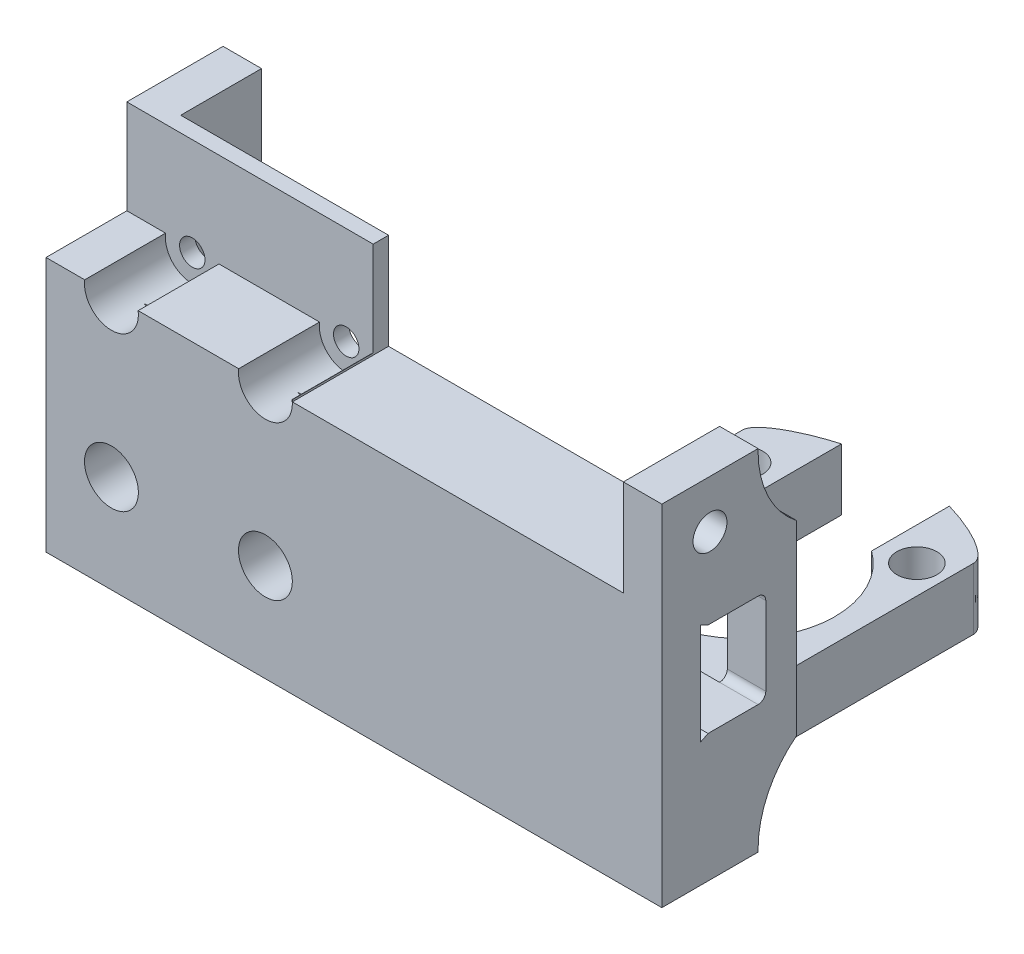
SolidWorks part; units mm, degrees
ref_plane "Front Plane" through (0, 0, 0) normal (0, 0, 1) x (1, 0, 0)
ref_plane "Top Plane" through (0, 0, 0) normal (0, 1, 0) x (1, 0, 0)
ref_plane "Right Plane" through (0, 0, 0) normal (1, 0, 0) x (0, 0, -1)
sketch "Sketch1" plane through (0, 0, 0) normal (0, 0, 1) x (1, 0, 0)
  line L1 (0, 0) -> (80, 0)
  line L2 (0, 0) -> (0, 45.4)
  line L3 (0, 45.4) -> (80, 45.4)
  line L4 (80, 0) -> (80, 45.4)
  line L5 (8.5, 32.7) -> (28.5, 32.7) construction
  line L6 (8.5, 32.7) -> (8.5, 12.7) construction
  line L7 (8.5, 12.7) -> (28.5, 12.7) construction
  line L8 (28.5, 32.7) -> (28.5, 12.7) construction
  circle A0 centre (8.5, 32.7) radius 1.65
  circle A1 centre (28.5, 32.7) radius 1.65
  circle A2 centre (28.5, 12.7) radius 1.65
  circle A3 centre (8.5, 12.7) radius 1.65
  dimension "D3" = 3.3
  dimension "D1" = 45.4
  dimension "D2" = 80
  dimension "D4" = 12.7
  dimension "D5" = 20
  dimension "D6" = 8.5
extrude "Boss-Extrude1" add sketch "Sketch1" along normal blind 12.5
sketch "Sketch2" plane through (0, 0, 0) normal (0, 0, -1) x (-1, 0, 0)
  line L0 (0, 0) -> (-80, 0) construction
  line L1 (0, 45.4) -> (-5, 45.4)
  line L2 (0, 45.4) -> (0, 0)
  line L3 (0, 0) -> (-5, 0)
  line L4 (-5, 45.4) -> (-5, 0)
  dimension "D1" = 5
extrude "Boss-Extrude2" add sketch "Sketch2" along normal blind 10.5
sketch "Sketch3" plane through (0, 0, 0) normal (0, 0, 1) x (1, 0, 0)
  line L0 (80, 0) -> (80, 45.4) construction
  line L1 (80, 28.8) -> (0, 28.8)
  line L2 (80, 28.8) -> (80, 16.6)
  line L3 (80, 16.6) -> (0, 16.6)
  line L4 (0, 28.8) -> (0, 16.6)
  line L5 (0, 0) -> (0, 45.4) construction
  line L6 (80, 22.7) -> (0, 22.7) construction
  point P10 (80, 22.7)
  dimension "D1" = 12.2
extrude "Cut-Extrude1" cut sketch "Sketch3" against normal through all and the other way blind 7.5
sketch "Sketch4" plane through (0, 0, 0) normal (0, 0, -1) x (-1, 0, 0)
  line L1 (-69.5, 0) -> (-39.5, 0)
  line L2 (-69.5, 0) -> (-69.5, 8)
  line L3 (-69.5, 8) -> (-39.5, 8)
  line L4 (-39.5, 0) -> (-39.5, 8)
  line L7 (-5, 0) -> (-80, 0) construction
  dimension "D1" = 8
  dimension "D2" = 30
  dimension "D3" = 39.5
extrude "Boss-Extrude3" add sketch "Sketch4" along normal blind 44.5
sketch "Sketch5" plane through (0, 8, 0) normal (0, 1, 0) x (1, 0, 0)
  line L0 (69.5, 44.5) -> (69.5, 0) construction
  line L1 (80, 0) -> (5, 0) construction
  circle A0 centre (54.4956, 23.5) radius 12
  dimension "D1" = 24
  dimension "D2" = 15.0044
  dimension "D3" = 23.5
extrude "Cut-Extrude2" cut sketch "Sketch5" against normal blind 45
sketch "Sketch6" plane through (0, 16.6, 0) normal (0, -1, 0) x (1, 0, 0)
  circle A3 centre (54.4956, -39.5013) radius 2.6
  circle A4 centre (65.8093, -34.815) radius 2.6
  circle A5 centre (43.1819, -34.815) radius 2.6
  dimension "D1" = 5.2
extrude "Cut-Extrude3" cut sketch "Sketch6" against normal through all both and the other way through all
fillet "Fillet1" radius 6 2 edges at (39.5, 4, -44.5) (69.5, 4, -44.5) second distance 15 conic rho 0.3 first distance on face at (39.5, 4, -22.25) first distance on face at (69.5, 4, -22.25)
sketch "Sketch8" plane through (0, 0, 12.5) normal (0, 0, 1) x (1, 0, 0)
  circle A0 centre (8.5, 32.7) radius 3.5
  circle A1 centre (28.5, 32.7) radius 3.5
  circle A2 centre (8.5, 12.7) radius 3.5
  circle A3 centre (28.5, 12.7) radius 3.5
  dimension "D1" = 7
extrude "Cut-Extrude5" cut sketch "Sketch8" against normal offset from surface (10.5 mm away) 2 up to face at (10.15, 12.7, 0)
sketch "Sketch12" plane through (0, 0, 12.5) normal (0, 0, 1) x (1, 0, 0)
  line L0 (80, 45.4) -> (0, 45.4) construction
  line L5 (0, 45.4) -> (45, 45.4)
  line L6 (0, 45.4) -> (0, 33.15)
  line L7 (0, 33.15) -> (45, 33.15)
  line L8 (45, 45.4) -> (45, 33.15)
  line L9 (0, 45.4) -> (0, 0) construction
  dimension "D1" = 12.25
  dimension "D2" = 45
extrude "Cut-Extrude8" cut sketch "Sketch12" against normal offset from surface (10.5 mm away) 2 up to face at (10.15, 32.7, 0)
sketch "Sketch13" plane through (0, 8, 0) normal (0, 1, 0) x (1, 0, 0)
  line L1 (61.4956, 51.1384) -> (47.4956, 51.1384)
  line L2 (61.4956, 51.1384) -> (61.4956, 27.8643)
  line L3 (61.4956, 27.8643) -> (47.4956, 27.8643)
  line L4 (47.4956, 51.1384) -> (47.4956, 27.8643)
  line L5 (61.4956, 51.1384) -> (47.4956, 27.8643) construction
  line L6 (61.4956, 27.8643) -> (47.4956, 51.1384) construction
  point P0 (54.4956, 39.5013)
  dimension "D1" = 14
extrude "Cut-Extrude10" cut sketch "Sketch13" against normal blind 10
sketch "Sketch14" plane through (0, 0, 0) normal (0, 0, -1) x (-1, 0, 0)
  line L1 (-80, 28.8) -> (0, 28.8)
  line L2 (-80, 28.8) -> (-80, 16.6)
  line L3 (-80, 16.6) -> (0, 16.6)
  line L4 (0, 28.8) -> (0, 16.6)
extrude "Boss-Extrude5" [suppressed] add sketch "Sketch14" against normal blind 0.5
sketch "Sketch15" plane through (0, 8, 0) normal (0, 1, 0) x (1, 0, 0)
  circle A0 centre (54.4956, 7.5013) radius 2.75
  dimension "D1" = 5.5
extrude "Boss-Extrude6" add sketch "Sketch15" along normal blind 2
sketch "Sketch16" plane through (0, 45.4, 0) normal (0, 1, 0) x (1, 0, 0)
  line L0 (39.5, 0) -> (69.5, 0) construction
  line L1 (75, 0) -> (32, 0)
  line L2 (75, 0) -> (75, -12.5)
  line L3 (75, -12.5) -> (32, -12.5)
  line L4 (32, 0) -> (32, -12.5)
  line L5 (80, -12.5) -> (45, -12.5) construction
  line L6 (80, -12.5) -> (80, 0) construction
  dimension "D1" = 32
  dimension "D2" = 5
extrude "Cut-Extrude11" cut sketch "Sketch16" against normal blind 12.5
sketch "Sketch17" plane through (80, 0, 0) normal (1, 0, 0) x (0, 0, -1)
  line L0 (-12.5, 45.4) -> (0, 45.4) construction
  line L1 (-6.25, 45.4) -> (-6.25, 28.8) construction
  line L2 (-7.5, 28.8) -> (0, 28.8) construction
  circle A0 centre (-6.25, 39.15) radius 2.2
  dimension "D1" = 4.4
  dimension "D2" = 6.25
extrude "Cut-Extrude12" cut sketch "Sketch17" against normal blind 10
sketch "Sketch18" plane through (80, 0, 0) normal (1, 0, 0) x (0, 0, -1)
  line L0 (-7.5, 28.8) -> (-6.5, 28.8)
  line L1 (-7.5, 28.8) -> (0, 28.8) construction
  line L2 (-6.5, 28.8) -> (-7.5, 29.3)
  line L3 (-7.5, 29.3) -> (-7.5, 28.8)
  line L4 (-7.5, 16.6) -> (-7.5, 16.1)
  line L5 (-7.5, 16.1) -> (-6.5, 16.6)
  line L6 (-7.5, 16.6) -> (0, 16.6) construction
  line L7 (-6.5, 16.6) -> (-7.5, 16.6)
  dimension "D1" = 0.5
  dimension "D2" = 1
  dimension "D3" = 1
  dimension "D4" = 0.5
extrude "Cut-Extrude13" cut sketch "Sketch18" against normal through all
sketch "Sketch19" plane through (0, 0, 0) normal (0, 0, -1) x (-1, 0, 0)
  line L0 (-80, 0) -> (-80, 16.6) construction
  line L1 (-75, 34.8) -> (-80, 34.8)
  line L2 (-75, 34.8) -> (-75, 10.6)
  line L3 (-75, 10.6) -> (-80, 10.6)
  line L4 (-80, 34.8) -> (-80, 10.6)
  line L5 (-5, 16.6) -> (-80, 16.6) construction
  line L6 (-80, 28.8) -> (-5, 28.8) construction
  line L7 (-75, 32.9) -> (-75, 45.4) construction
  dimension "D1" = 6
  dimension "D2" = 6
extrude "Boss-Extrude7" add sketch "Sketch19" along normal blind 5
sketch "Sketch20" plane through (80, 0, 0) normal (1, 0, 0) x (0, 0, -1)
  line L0 (0, 28.8) -> (0, 16.6)
  line L1 (0, 28.8) -> (1, 28.8)
  line L2 (0, 16.6) -> (1, 16.6)
  line L3 (1, 28.8) -> (1, 16.6)
  dimension "D1" = 1
extrude "Cut-Extrude14" cut sketch "Sketch20" against normal through all
sketch "Sketch21" plane through (0, 16.6, 0) normal (0, 1, 0) x (1, 0, 0)
  line L0 (5, 0) -> (5, 10.5) construction
  line L1 (0, 10.5) -> (5, 10.5)
  line L2 (0, 10.5) -> (0, 1)
  line L3 (0, 1) -> (5, 1)
  line L4 (5, 10.5) -> (5, 1)
  dimension "D1" = 9.5
extrude "Boss-Extrude8" add sketch "Sketch21" along normal up to surface (12.2 mm away) up to face at (40, 28.8, -1.25)
fillet "Fillet2" radius 1 4 edges at (77.5, 16.6, -1) (77.5, 28.8, -1) (2.5, 16.6, -1) (2.5, 28.8, -1)
fillet "Fillet3" radius 13 2 edges at (77.5, 10.6, 0) (77.5, 34.8, 0)
chamfer "Chamfer1" distance 2 angle 45 1 edges at (54.4956, 10, -4.7513)
